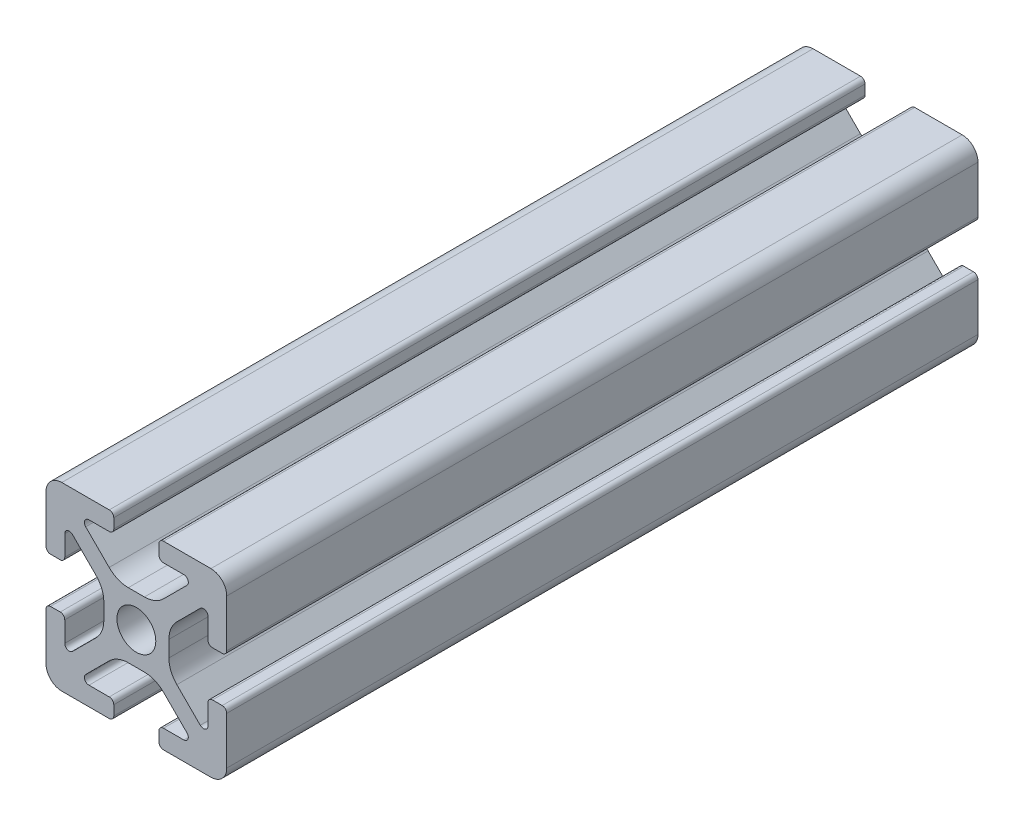
SolidWorks part; units mm, degrees
ref_plane "Front Plane" through (0, 0, 0) normal (0, 0, 1) x (1, 0, 0)
ref_plane "Top Plane" through (0, 0, 0) normal (0, 1, 0) x (1, 0, 0)
ref_plane "Right Plane" through (0, 0, 0) normal (1, 0, 0) x (0, 0, -1)
sketch "Sketch2" plane through (0, 0, 0) normal (0, 0, 1) x (1, 0, 0)
  line L0 (0, 10) -> (0, -10) construction
  line L1 (-10, 0) -> (10, 0) construction
  line L2 (2.5, -10) -> (10, -10)
  line L3 (10, -10) -> (10, -2.5)
  line L4 (2.5, -10) -> (2.5, -7.9246)
  line L5 (2.5, -7.9246) -> (6.4571, -7.9246)
  line L6 (6.4571, -7.9246) -> (2.1325, -3.6)
  line L7 (0, 0) -> (10, -10) construction
  line L8 (10, -2.5) -> (7.9246, -2.5)
  line L9 (7.9246, -2.5) -> (7.9246, -6.4571)
  line L10 (7.9246, -6.4571) -> (3.6, -2.1325)
  line L11 (5.7623, -4.2948) -> (4.2948, -5.7623) construction
  circle A0 centre (0, 0) radius 2.15
  arc A1 (5.25, -7.9246) -> (5.6036, -7.0711) centre (5.25, -7.4246) ccw construction
  point P8 (0, -3.6)
  point P16 (5.0286, -5.0286)
  dimension "Center Hole Diameter" = 4.3
  dimension "D3" = 0.5
  dimension "Rail Height" = 20
  dimension "Rail Width" = 20
  dimension "T-Slot Width" = 5
  dimension "Slot Depth" = 6.4
  dimension "Slot Inner Width" = 11.5
sketch "Sketch3" plane through (0, 0, 0) normal (1, 0, 0) x (0, 0, -1)
  line L0 (-41.57, -10) -> (41.57, -10) construction
  line L1 (-16.17, 0) -> (16.17, 0) construction
  line L2 (0, 10) -> (0, -10) construction
  line L3 (0, 10) -> (0, -10) construction
  point P6 (-16.17, 0)
  point P8 (16.17, 0)
  dimension "Length" = 83.14
  dimension "D1" = 25.4
sketch "Sketch4" plane through (0, 0, 0) normal (0, 0, 1) x (1, 0, 0)
  line L0 (3, -10) -> (8.25, -10)
  line L1 (2.5, -10) -> (10, -10) construction
  line L2 (2.5, -10) -> (2.5, -7.9246) construction
  line L3 (2.5, -7.9246) -> (6.4571, -7.9246) construction
  line L4 (2.5, -8.4246) -> (2.5, -9.5)
  line L5 (3, -7.9246) -> (5.25, -7.9246)
  line L6 (0, -3.6) -> (0.8898, -3.6)
  line L7 (6.4571, -7.9246) -> (2.1325, -3.6) construction
  line L8 (3.0112, -4.4787) -> (5.6036, -7.0711)
  line L9 (10, -10) -> (10, -2.5) construction
  line L10 (7.9246, -6.4571) -> (3.6, -2.1325) construction
  line L11 (7.9246, -2.5) -> (7.9246, -6.4571) construction
  line L12 (7.9246, -5.25) -> (7.9246, -3)
  line L13 (10, -2.5) -> (7.9246, -2.5) construction
  line L14 (8.4246, -2.5) -> (9.5, -2.5)
  line L15 (10, -3) -> (10, -8.25)
  line L16 (7.0711, -5.6036) -> (4.4787, -3.0112)
  line L17 (3.6, 0) -> (3.6, -0.8898)
  line L18 (-10, 0) -> (10, 0) construction
  line L19 (0, -3.6) -> (0, -2.15)
  line L20 (0, 10) -> (0, -10) construction
  line L21 (3.6, 0) -> (2.15, 0)
  arc A0 (2.5, -9.5) -> (3, -10) centre (3, -9.5) ccw
  arc A1 (5.25, -7.9246) -> (5.6036, -7.0711) centre (5.25, -7.4246) ccw construction
  arc A2 (2.5, -8.4246) -> (3, -7.9246) centre (3, -8.4246) cw
  arc A3 (5.25, -7.9246) -> (5.6036, -7.0711) centre (5.25, -7.4246) ccw
  arc A4 (0.8898, -3.6) -> (3.0112, -4.4787) centre (0.8898, -6.6) cw
  arc A5 (8.25, -10) -> (10, -8.25) centre (8.25, -8.25) ccw
  arc A6 (7.0711, -5.6036) -> (7.9246, -5.25) centre (7.4246, -5.25) ccw
  arc A7 (7.9246, -3) -> (8.4246, -2.5) centre (8.4246, -3) cw
  arc A8 (9.5, -2.5) -> (10, -3) centre (9.5, -3) cw
  arc A9 (4.4787, -3.0112) -> (3.6, -0.8898) centre (6.6, -0.8898) cw
  circle A10 centre (0, 0) radius 2.15 construction
  arc A11 (0, -2.15) -> (2.15, 0) centre (0, 0) ccw
  dimension "D1" = 1.75
  dimension "D2" = 3
extrude "Boss-Extrude1" add sketch "Sketch4" along normal mid plane 83.14
mirror "Mirror1" about plane through (0, 0, 0) normal (1, 0, 0) of bodies 134
mirror "Mirror2" about plane through (0, 0, 0) normal (0, 1, 0) of bodies 135
equation "\"D3@Sketch2\"=\"T-Slot Width@Sketch2\"*0.1"
equation "\"D1@Sketch4\"=\"D3@Sketch2\"*3.5"
equation "\"D2@Sketch4\"=\"D3@Sketch2\"*6"
equation "\"D1@Boss-Extrude1\"=\"Length@Sketch3\""
